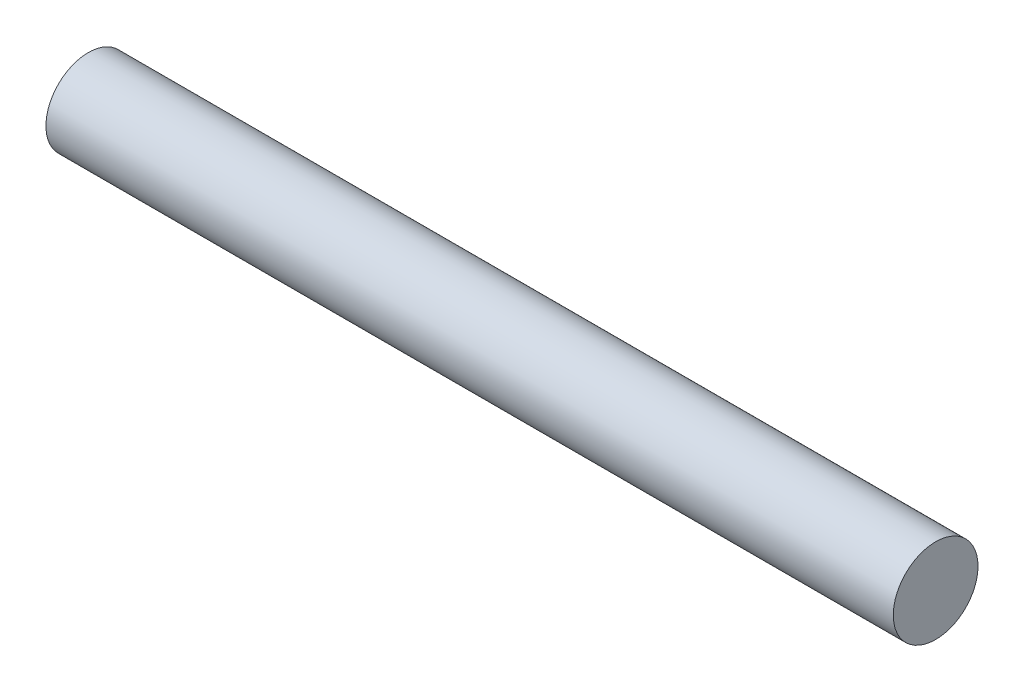
SolidWorks part; units mm, degrees
ref_plane "Спереди" through (0, 0, 0) normal (0, 0, 1) x (1, 0, 0)
ref_plane "Сверху" through (0, 0, 0) normal (0, 1, 0) x (1, 0, 0)
ref_plane "Справа" through (0, 0, 0) normal (1, 0, 0) x (0, 0, -1)
sketch "Эскиз1" plane through (0, 0, 0) normal (1, 0, 0) x (0, 0, -1)
  circle A0 centre (0, 0) radius 5
  dimension "D1" = 10
extrude "Бобышка-Вытянуть1" add sketch "Эскиз1" along normal mid plane 100
